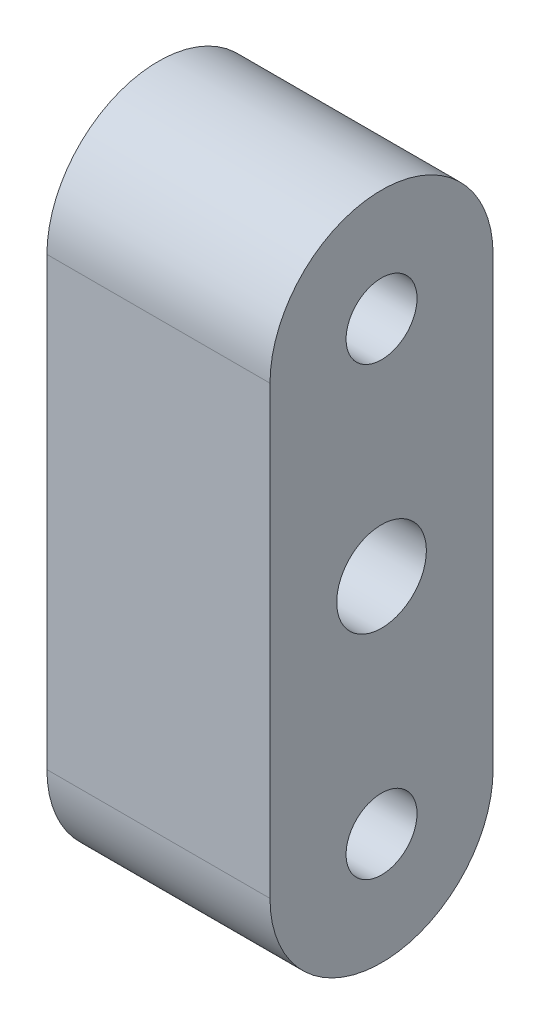
SolidWorks part; units mm, degrees
ref_plane "Front" through (0, 0, 0) normal (0, 0, 1) x (1, 0, 0)
ref_plane "Top" through (0, 0, 0) normal (0, 1, 0) x (1, 0, 0)
ref_plane "Right" through (0, 0, 0) normal (1, 0, 0) x (0, 0, -1)
sketch "Sketch1" plane through (0, 0, 0) normal (1, 0, 0) x (0, 0, -1)
  line L0 (0, 12.7) -> (0, -12.7) construction
  line L1 (6.35, 12.7) -> (6.35, -12.7)
  line L2 (-6.35, 12.7) -> (-6.35, -12.7)
  arc A0 (6.35, 12.7) -> (-6.35, 12.7) centre (0, 12.7) ccw
  arc A1 (-6.35, -12.7) -> (6.35, -12.7) centre (0, -12.7) ccw
  point P2 (0, 0)
  dimension "D1" = 12.7
  dimension "D2" = 25.4
extrude "Boss-Extrude1" add sketch "Sketch1" along normal blind 12.7
hole_wizard "1/4-20 Tapped Hole1" positions "Sketch2" profile "Sketch3" tap size "1/4-20" standard "ANSI Inch" end condition through all
sketch "Sketch2" plane through (12.7, 0, 0) normal (1, 0, 0) x (0, 0, -1)
  point P0 (0, 0)
sketch "Sketch3" plane through (12.7, 0, 0) normal (0, 1, 0) x (0, 0, -1)
  line L0 (0, 0) -> (0, 12.7)
  line L1 (0, 12.7) -> (2.5527, 12.7)
  line L2 (2.5527, 12.7) -> (2.5527, 0)
  line L5 (2.5527, 0) -> (0, 0)
  line L11 (0, -6.35) -> (0, 107.95) construction
  dimension "Thru Tap Drill Dia." = 5.1054
  dimension "Thru Tap Drill Depth" = 12.7
cosmetic thread "Hole Thread1" parameters "D2"=6.35
hole_wizard "#10-32 Tapped Hole1" positions "Sketch4" profile "Sketch5" tap size "#10-32" standard "ANSI Inch" end condition through all
sketch "Sketch4" plane through (12.7, 0, 0) normal (1, 0, 0) x (0, 0, -1)
  point P0 (0, 12.7)
  point P2 (0, -12.7)
sketch "Sketch5" plane through (12.7, 12.7, 0) normal (0, 1, 0) x (0, 0, -1)
  line L0 (0, 0) -> (0, 12.7)
  line L1 (0, 12.7) -> (2.0193, 12.7)
  line L2 (2.0193, 12.7) -> (2.0193, 0)
  line L5 (2.0193, 0) -> (0, 0)
  line L11 (0, -6.35) -> (0, 107.95) construction
  dimension "Thru Tap Drill Dia." = 4.0386
  dimension "Thru Tap Drill Depth" = 12.7
cosmetic thread "Hole Thread2" parameters "D2"=4.826
cosmetic thread "Hole Thread3" parameters "D2"=4.826
